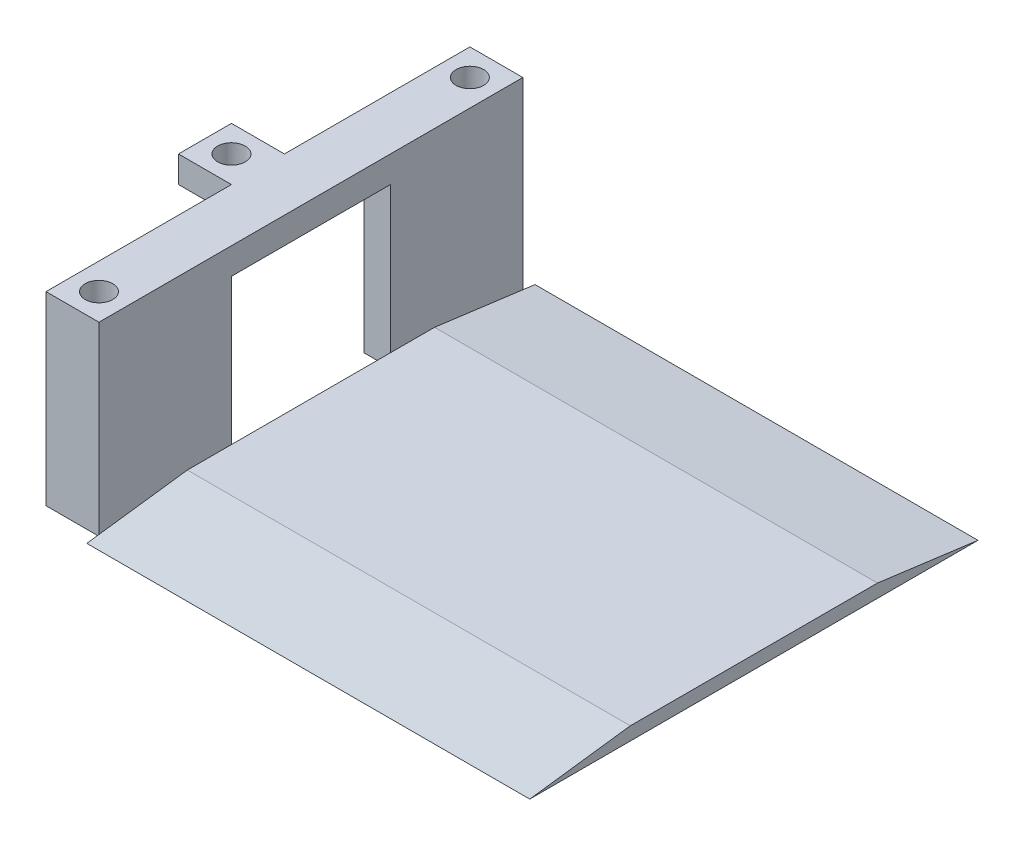
SolidWorks part; units mm, degrees
ref_plane "Front Plane" through (0, 0, 0) normal (0, 0, 1) x (1, 0, 0)
ref_plane "Top Plane" through (0, 0, 0) normal (0, 1, 0) x (1, 0, 0)
ref_plane "Right Plane" through (0, 0, 0) normal (1, 0, 0) x (0, 0, -1)
sketch "Sketch1" plane through (0, 0, 0) normal (0, 1, 0) x (1, 0, 0)
  line L1 (0, 0) -> (106.172, 0)
  line L2 (0, 0) -> (0, 107.442)
  line L3 (0, 107.442) -> (106.172, 107.442)
  line L4 (106.172, 0) -> (106.172, 107.442)
  dimension "D1" = 107.442
  dimension "D2" = 106.172
extrude "Boss-Extrude1" add sketch "Sketch1" along normal blind 3.175
sketch "Sketch3" plane through (0, 0, 0) normal (0, 1, 0) x (1, 0, 0)
  line L0 (0, 53.721) -> (106.172, 53.721) construction
  line L5 (-12.7, 91.821) -> (0, 91.821)
  line L6 (-12.7, 91.821) -> (-12.7, 104.521)
  line L7 (-12.7, 104.521) -> (0, 104.521)
  line L8 (0, 91.821) -> (0, 104.521)
  line L9 (-12.7, 91.821) -> (0, 104.521) construction
  line L10 (-12.7, 104.521) -> (0, 91.821) construction
  line L11 (0, 107.442) -> (0, 0) construction
  line L12 (106.172, 0) -> (106.172, 107.442) construction
  line L13 (-12.7, 2.921) -> (0, 15.621) construction
  line L14 (-12.7, 15.621) -> (0, 2.921) construction
  line L15 (0, 15.621) -> (0, 2.921)
  line L16 (-12.7, 2.921) -> (0, 2.921)
  line L17 (-12.7, 15.621) -> (-12.7, 2.921)
  line L18 (-12.7, 15.621) -> (0, 15.621)
  circle A1 centre (-6.35, 98.171) radius 3.302
  circle A2 centre (-6.35, 9.271) radius 3.302
  point P0 (-6.35, 98.171)
  point P21 (-6.35, 9.271)
  dimension "D2" = 6.604
  dimension "D1" = 12.7
  dimension "D3" = 12.7
  dimension "D4" = 88.9
extrude "Boss-Extrude2" add sketch "Sketch3" along normal blind 44.45
sketch "Sketch4" plane through (106.172, 0, 0) normal (1, 0, 0) x (0, 0, -1)
  line L5 (0, 0) -> (24.0965, 3.175)
  line L7 (0, 3.175) -> (107.442, 3.175) construction
  line L8 (24.0965, 3.175) -> (0, 3.175)
  line L9 (0, 3.175) -> (0, 0)
  line L10 (53.721, 3.175) -> (53.721, 0) construction
  line L11 (0, 0) -> (107.442, 0) construction
  line L12 (107.442, 3.175) -> (107.442, 0)
  line L13 (83.3455, 3.175) -> (107.442, 3.175)
  line L14 (107.442, 0) -> (83.3455, 3.175)
extrude "Cut-Extrude1" cut sketch "Sketch4" against normal up to surface (106.172 mm away) up to face at (0, 23.8125, -9.271)
sketch "Sketch6" plane through (0, 0, -91.821) normal (0, 0, 1) x (1, 0, 0)
  line L0 (0, 44.45) -> (0, 2.0582) construction
  line L1 (-12.7, 44.45) -> (0, 44.45)
  line L2 (-12.7, 44.45) -> (-12.7, 38.1)
  line L3 (-12.7, 38.1) -> (0, 38.1)
  line L4 (0, 44.45) -> (0, 38.1)
  dimension "D1" = 6.35
extrude "Boss-Extrude3" add sketch "Sketch6" along normal up to surface (76.2 mm away) up to face at (-5.08, 18.1916, -15.621)
sketch "Sketch11" plane through (0, 44.45, 0) normal (0, 1, 0) x (1, 0, 0)
  line L0 (-12.7, 104.521) -> (-12.7, 2.921) construction
  line L1 (-12.7, 60.071) -> (-25.4, 60.071)
  line L2 (-12.7, 60.071) -> (-12.7, 47.371)
  line L3 (-12.7, 47.371) -> (-25.4, 47.371)
  line L4 (-25.4, 60.071) -> (-25.4, 47.371)
  line L5 (0, 53.721) -> (-28.0072, 53.721) construction
  line L6 (-12.7, 60.071) -> (-25.4, 47.371) construction
  line L7 (-25.4, 60.071) -> (-12.7, 47.371) construction
  line L9 (0, 2.921) -> (0, 104.521) construction
  circle A0 centre (-19.05, 53.721) radius 3.302
  dimension "D1" = 12.7
  dimension "D4" = 6.604
  dimension "D2" = 12.7
extrude "Boss-Extrude5" add sketch "Sketch11" against normal blind 6.35
sketch "Sketch12" plane through (0, 0, 0) normal (0, -1, 0) x (1, 0, 0)
  line L5 (0, -91.821) -> (0, -15.621) construction
  line L6 (0, -34.671) -> (-6.35, -34.671)
  line L7 (0, -34.671) -> (0, -15.621)
  line L8 (0, -15.621) -> (-6.35, -15.621)
  line L9 (-6.35, -34.671) -> (-6.35, -15.621)
  line L10 (0, -15.621) -> (-12.7, -15.621) construction
  line L11 (106.172, -53.721) -> (-53.2514, -53.721) construction
  line L12 (106.172, 0) -> (106.172, -107.442) construction
  line L13 (-6.35, -72.771) -> (-6.35, -91.821)
  line L14 (0, -91.821) -> (-6.35, -91.821)
  line L15 (0, -72.771) -> (0, -91.821)
  line L16 (0, -72.771) -> (-6.35, -72.771)
  dimension "D1" = 38.1
extrude "Boss-Extrude6" add sketch "Sketch12" against normal up to surface (38.1 mm away) up to face at (-12.7, 38.1, -53.721)
equation "\"tightTol\" = 0.005in"
equation "\"normTol\"= 0.01in"
equation "\"looseTol\"= 0.02in"
equation "\"4.250000in-\"= 4.25"
equation "\"D1@Sketch1\"=4.25-\"looseTol\""
equation "\"D2@Sketch3\"=\"normTol\"+0.250000in"
equation "\"D4@Sketch11\"=\"normTol\"+0.250000in"
equation "\"D2@Sketch1\"=4.200000in-\"looseTol\""
